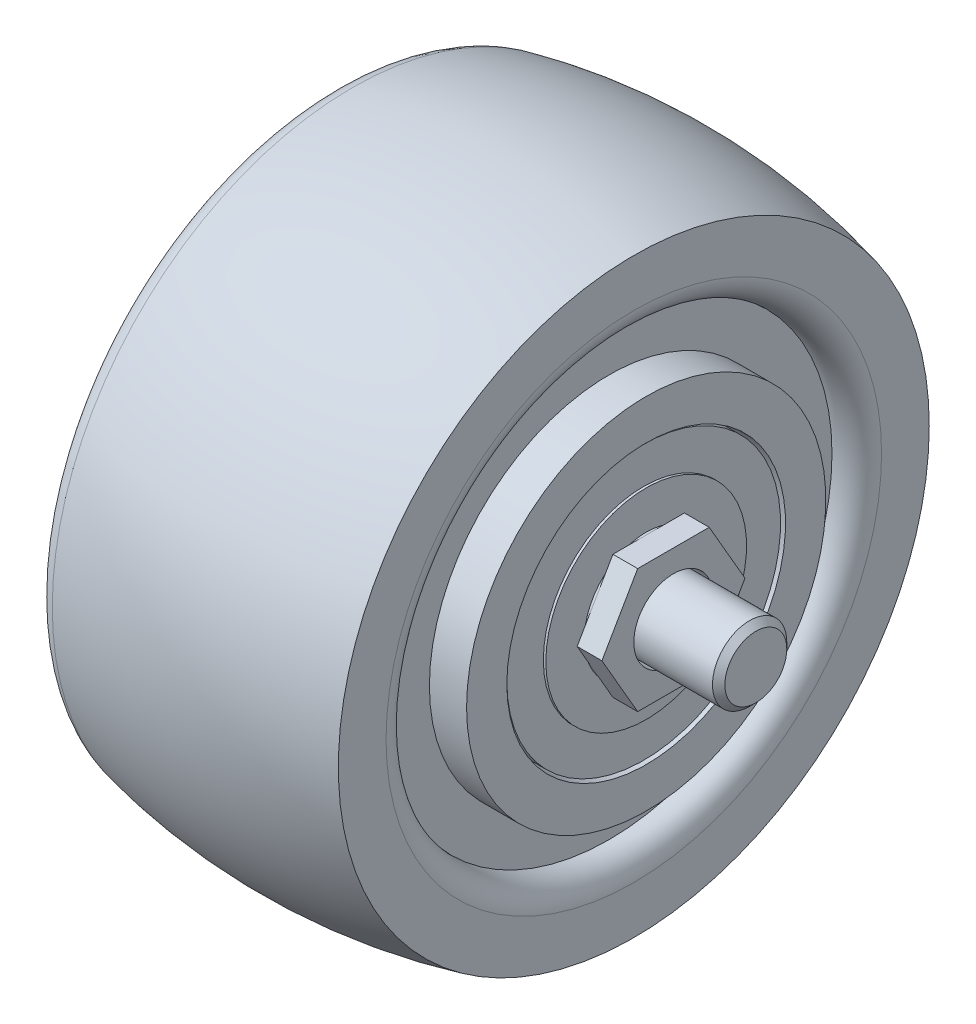
SolidWorks part; units mm, degrees
ref_plane "Front Plane" through (0, 0, 0) normal (0, 0, 1) x (1, 0, 0)
ref_plane "Top Plane" through (0, 0, 0) normal (0, 1, 0) x (1, 0, 0)
ref_plane "Right Plane" through (0, 0, 0) normal (1, 0, 0) x (0, 0, -1)
sketch "Sketch1" plane through (0, 0, 0) normal (1, 0, 0) x (0, 0, -1)
  circle A0 centre (0, 0) radius 25.35
  dimension "D1" = 50.7
extrude "Boss-Extrude1" add sketch "Sketch1" along normal blind 12.15 and the other way blind 12.15
sketch "Sketch2" plane through (0, 0, 0) normal (0, 0, 1) x (1, 0, 0)
  line L0 (0, 0) -> (-48.3586, 0) construction
  line L1 (0, 0) -> (0, -24.65) construction
  line L2 (12.15, 25.35) -> (-12.15, 25.35) construction
  line L4 (15.995, 22.7226) -> (16.3985, 22.7226)
  line L5 (0, 25.35) -> (-8.1733, 25.35) construction
  line L6 (-15.995, 22.7226) -> (-15.995, 31.6473)
  line L7 (-15.995, 31.6473) -> (16.3985, 31.6473)
  line L8 (16.3985, 22.7226) -> (16.3985, 31.6473)
  arc A0 (15.995, 22.7226) -> (-15.995, 22.7226) centre (0, -24.65) ccw
  dimension "D1" = 100
revolve "Cut-Revolve1" cut sketch "Sketch2" angle 360 about L0 other way angle 360
fillet "Fillet1" radius 2 1 edges at (-12.15, 0, -23.8513)
sketch "Sketch3" plane through (-12.15, 0, 0) normal (-1, 0, 0) x (0, 0, 1)
  circle A0 centre (0, 0) radius 18
  dimension "D1" = 36
extrude "Cut-Extrude1" cut sketch "Sketch3" against normal blind 2
mirror "Mirror1" about plane through (0, 0, 0) normal (1, 0, 0) of "Cut-Extrude1"
fillet "Fillet2" radius 2 2 edges at (-12.15, 0, 18) (12.15, 0, 18)
sketch "Sketch4" plane through (-10.15, 0, 0) normal (-1, 0, 0) x (0, 0, 1)
  circle A0 centre (0, 0) radius 14.5
  dimension "D1" = 29
extrude "Boss-Extrude2" add sketch "Sketch4" along normal blind 3
mirror "Mirror2" about plane through (0, 0, 0) normal (1, 0, 0) of "Boss-Extrude2"
sketch "Sketch5" plane through (-13.15, 0, 0) normal (-1, 0, 0) x (0, 0, 1)
  circle A0 centre (0, 0) radius 11.25
  dimension "D1" = 22.5
extrude "Cut-Extrude2" cut sketch "Sketch5" against normal blind 3
sketch "Sketch6" plane through (-10.15, 0, 0) normal (-1, 0, 0) x (0, 0, 1)
  circle A2 centre (0, 0) radius 11.05
  circle A3 centre (0, 0) radius 11.05
  dimension "D1" = 0.2
extrude "Boss-Extrude3" add sketch "Sketch6" along normal blind 2.8
sketch "Sketch7" plane through (-12.95, 0, 0) normal (-1, 0, 0) x (0, 0, 1)
  circle A0 centre (0, 0) radius 8.1034
extrude "Boss-Extrude4" add sketch "Sketch7" along normal blind 0.2
mirror "Mirror4" about plane through (0, 0, 0) normal (1, 0, 0) of "Boss-Extrude4", "Boss-Extrude3", "Cut-Extrude2"
sketch "Sketch8" plane through (0, 0, 0) normal (1, 0, 0) x (0, 0, -1)
  circle A0 centre (0, 0) radius 3
  dimension "D1" = 6
extrude "Boss-Extrude5" add sketch "Sketch8" along normal blind 22 and the other way blind 22
chamfer "Chamfer1" distance 0.5 angle 45 2 edges at (22, 0, -3) (-22, 0, -3)
sketch "Sketch9" plane through (-13.15, 0, 0) normal (-1, 0, 0) x (0, 0, 1)
  circle A0 centre (0, 0) radius 5
  circle A1 centre (0, 0) radius 3
  dimension "D1" = 10
extrude "Boss-Extrude6" add sketch "Sketch9" along normal blind 0.2
mirror "Mirror5" about plane through (0, 0, 0) normal (1, 0, 0) of "Boss-Extrude6"
sketch "Sketch10" plane through (13.35, 0, 0) normal (1, 0, 0) x (0, 0, -1)
  line L1 (5.7735, 0) -> (2.8868, 5)
  line L2 (2.8868, 5) -> (-2.8868, 5)
  line L3 (-2.8868, 5) -> (-5.7735, 0)
  line L4 (-5.7735, 0) -> (-2.8868, -5)
  line L5 (-2.8868, -5) -> (2.8868, -5)
  line L6 (2.8868, -5) -> (5.7735, 0)
  circle A0 centre (0, 0) radius 5 construction
  circle A1 centre (0, 0) radius 3.2
  dimension "D2" = 6.4
  dimension "D1" = 10
extrude "Boss-Extrude7" add sketch "Sketch10" along normal blind 2
mirror "Mirror6" about plane through (0, 0, 0) normal (1, 0, 0) of "Boss-Extrude7"
sketch "Sketch11" plane through (-10.15, 0, 0) normal (-1, 0, 0) x (0, 0, 1)
  circle A0 centre (1.3383, -16.1453) radius 0.7551
  dimension "D1" = 1.5102
extrude "Cut-Extrude3" cut sketch "Sketch11" against normal blind 2
